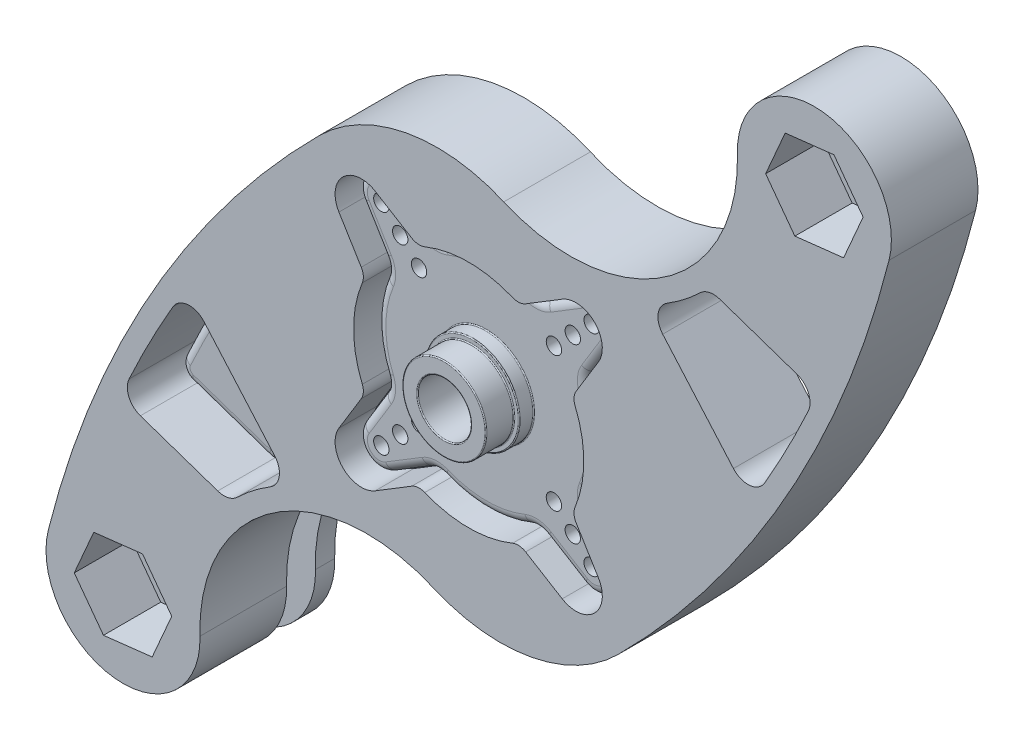
SolidWorks part; units mm, degrees
ref_plane "Front Plane" through (0, 0, 0) normal (0, 0, 1) x (1, 0, 0)
ref_plane "Top Plane" through (0, 0, 0) normal (0, 1, 0) x (1, 0, 0)
ref_plane "Right Plane" through (0, 0, 0) normal (1, 0, 0) x (0, 0, -1)
sketch "Sketch2" plane through (0, 0, 0) normal (0, 0, 1) x (1, 0, 0)
  line L1 (0, 0) -> (14.055, 0)
  line L2 (0, 0) -> (0, 14.055)
  line L3 (0, 14.055) -> (14.055, 14.055)
  line L4 (14.055, 0) -> (14.055, 14.055)
  dimension "D1" = 14.055
  dimension "D2" = 14.055
extrude "Boss-Extrude1" add sketch "Sketch2" along normal blind 2.15
sketch "Sketch3" plane through (0, 0, 2.15) normal (0, 0, 1) x (1, 0, 0)
  line L1 (14.055, 0) -> (14.055, 14.055) construction
  line L2 (0.9991, 9.98) -> (3.8759, 5.2647)
  line L3 (4.075, 13.0559) -> (8.7903, 10.1791)
  line L4 (0, 14.055) -> (14.055, 0) construction
  line L5 (14.055, 11.46) -> (14.055, 14.055)
  line L6 (14.055, 14.055) -> (0, 14.055)
  line L7 (0, 14.055) -> (0, 0)
  line L8 (0, 0) -> (2.595, 0)
  line L10 (0, 0) -> (14.055, 0) construction
  arc A0 (14.055, 11.46) -> (2.595, 0) centre (14.055, 0) ccw construction
  arc A1 (0.9991, 9.98) -> (4.075, 13.0559) centre (2.9095, 11.1455) cw
  arc A2 (3.8759, 5.2647) -> (2.595, 0) centre (14.055, 0) ccw
  arc A3 (8.7903, 10.1791) -> (14.055, 11.46) centre (14.055, 0) cw
  point P11 (1.3271, 12.7279)
  dimension "D1" = 11.46
  dimension "D4" = 18
  dimension "D2" = 6.95
  dimension "D3" = 4.35
extrude "Cut-Extrude3" cut sketch "Sketch3" against normal blind 2.15
sketch "Sketch4" plane through (0, 0, 2.15) normal (0, 0, 1) x (1, 0, 0)
  line L0 (14.055, 0) -> (14.055, 11.46) construction
  line L1 (2.595, 0) -> (14.055, 0) construction
  arc A0 (14.055, 1.56) -> (12.495, 0) centre (14.055, 0) ccw
  dimension "D1" = 1.56
extrude "Cut-Extrude1" cut sketch "Sketch4" against normal blind 2.15 and the other way through all
sketch "Sketch5" plane through (0, 0, 2.15) normal (0, 0, 1) x (1, 0, 0)
  line L0 (1.3271, 12.7279) -> (12.9519, 1.1031) construction
  circle A0 centre (7.0476, 7.0074) radius 0.8
  circle A1 centre (5.0889, 8.9661) radius 0.8
  circle A2 centre (3.1302, 10.9248) radius 0.8
  arc A3 (4.075, 13.0559) -> (0.9991, 9.98) centre (2.9095, 11.1455) ccw construction
  arc A4 (14.055, 1.56) -> (12.495, 0) centre (14.055, 0) ccw construction
  dimension "D1" = 1.6
  dimension "D3" = 2.77
  dimension "D2" = 2.55
  dimension "D4" = 2.77
extrude "Cut-Extrude4" cut sketch "Sketch5" against normal blind 2.15
fillet "Fillet1" radius 2 2 edges at (8.7903, 10.1791, 1.075) (3.8759, 5.2647, 1.075)
fillet "Fillet2" radius 1 7 edges at (2.8137, 2.2282, 2.15) (3.6066, 5.2905, 2.15) (2.1596, 8.0779, 2.15) (1.3271, 12.7279, 2.15) (5.9771, 11.8954, 2.15) (8.7645, 10.4484, 2.15) (11.8268, 11.2413, 2.15)
sketch "Sketch6" plane through (0, 0, 2.15) normal (0, 0, 1) x (1, 0, 0)
  line L2 (14.055, 1.56) -> (14.055, 10.46) construction
  line L3 (3.595, 0) -> (12.495, 0) construction
  line L4 (14.055, 4.9) -> (14.055, 2.765)
  line L5 (11.29, 0) -> (9.155, 0)
  arc A0 (14.055, 2.765) -> (11.29, 0) centre (14.055, 0) ccw
  arc A1 (14.055, 4.9) -> (9.155, 0) centre (14.055, 0) ccw
  dimension "D1" = 2.765
  dimension "D2" = 4.9
extrude "Boss-Extrude2" add sketch "Sketch6" along normal blind 1.5
sketch "Sketch7" plane through (0, 0, 3.65) normal (0, 0, 1) x (1, 0, 0)
  line L0 (14.055, 2.765) -> (14.055, 4.9) construction
  line L1 (9.155, 0) -> (11.29, 0) construction
  line L2 (14.055, 4.35) -> (14.055, 2.765)
  line L3 (11.29, 0) -> (9.705, 0)
  arc A0 (14.055, 2.765) -> (11.29, 0) centre (14.055, 0) ccw
  arc A1 (14.055, 2.765) -> (11.29, 0) centre (14.055, 0) ccw construction
  arc A2 (14.055, 4.35) -> (9.705, 0) centre (14.055, 0) ccw
  dimension "D1" = 4.35
extrude "Boss-Extrude3" add sketch "Sketch7" along normal blind 2.9
fillet "Fillet3" radius 0.1 5 edges at (10.5902, 3.4648, 2.15) (10.5902, 3.4648, 3.65) (10.9791, 3.0759, 3.65) (12.0998, 1.9552, 6.55) (10.9791, 3.0759, 6.55)
sketch "Sketch8" plane through (0, 0, 0) normal (0, 0, -1) x (-1, 0, 0)
  line L0 (-14.055, 1.56) -> (-14.055, 11.46) construction
  line L1 (-2.595, 0) -> (-12.495, 0) construction
  line L2 (-12.495, 0) -> (-11.305, 0)
  line L3 (-14.055, 2.75) -> (-14.055, 1.56)
  arc A0 (-14.055, 1.56) -> (-12.495, 0) centre (-14.055, 0) cw
  arc A1 (-12.495, 0) -> (-14.055, 1.56) centre (-14.055, 0) ccw construction
  arc A2 (-14.055, 2.75) -> (-11.305, 0) centre (-14.055, 0) cw
  dimension "D1" = 2.75
extrude "Cut-Extrude5" cut sketch "Sketch8" against normal blind 1.4
mirror "Mirror1" about plane through (0, 0, 2.15) normal (0, 1, 0) of bodies 109 104
mirror "Mirror2" about plane through (14.055, 0, 2.15) normal (-1, 0, 0) of bodies 105
sketch "Sketch9" plane through (0, 0, 0) normal (0, 0, -1) x (-1, 0, 0)
  line L0 (21.866, -35.921) -> (-14.055, 0) construction
  line L1 (-14.055, 0) -> (-29.6113, -15.5563) construction
  line L2 (-29.6113, -15.5563) -> (-35.3919, -9.7758) construction
  line L3 (-14.055, 0) -> (1.5013, 15.5563) construction
  line L4 (1.5013, 15.5563) -> (-6.7407, 23.7984) construction
  line L5 (-27.1365, -13.0815) -> (-29.6113, -15.5563)
  line L6 (-0.9735, 13.0815) -> (1.5013, 15.5563)
  line L16 (-19.9704, 11.1618) -> (-23.7746, 13.4827)
  line L17 (-27.5377, 9.7196) -> (-25.2168, 5.9154)
  line L18 (-25.2168, -5.9154) -> (-27.5377, -9.7196)
  line L19 (-23.7746, -13.4827) -> (-19.9704, -11.1618)
  line L20 (-8.1396, -11.1618) -> (-4.3354, -13.4827)
  line L21 (-0.5723, -9.7196) -> (-2.8932, -5.9154)
  line L22 (-2.8932, 5.9154) -> (-0.5723, 9.7196)
  line L23 (-4.3354, 13.4827) -> (-8.1396, 11.1618)
  line L27 (-23.7746, -13.4827) -> (-19.9704, -11.1618)
  line L28 (-8.1396, -11.1618) -> (-4.3354, -13.4827)
  line L29 (-0.5723, -9.7196) -> (-2.8932, -5.9154)
  line L30 (-2.8932, 5.9154) -> (-0.5723, 9.7196)
  arc A0 (-29.6113, -15.5563) -> (-10.4093, -19.202) centre (-17.3331, -3.2781) ccw
  arc A1 (-10.4093, -19.202) -> (13.87, -35.6702) centre (-3.4855, -35.1259) cw
  arc A2 (13.87, -35.6702) -> (29.6221, -33.9607) centre (21.866, -35.921) ccw
  arc A3 (1.5013, 15.5563) -> (29.6221, -33.9607) centre (-74.2763, -60.2213) cw
  circle A12 centre (21.866, -35.921) radius 2.159
  arc A32 (-9.493, 11.0557) -> (-18.617, 11.0557) centre (-14.055, 0) ccw
  arc A33 (-19.9704, 11.1618) -> (-18.617, 11.0557) centre (-19.1892, 12.4423) ccw
  arc A34 (-23.7746, 13.4827) -> (-27.5377, 9.7196) centre (-25.2005, 11.1455) ccw
  arc A35 (-25.1107, 4.562) -> (-25.2168, 5.9154) centre (-26.4973, 5.1342) ccw
  arc A36 (-25.1107, 4.562) -> (-25.1107, -4.562) centre (-14.055, 0) ccw
  arc A37 (-25.2168, -5.9154) -> (-25.1107, -4.562) centre (-26.4973, -5.1342) ccw
  arc A38 (-27.5377, -9.7196) -> (-23.7746, -13.4827) centre (-25.2005, -11.1455) ccw
  arc A39 (-18.617, -11.0557) -> (-19.9704, -11.1618) centre (-19.1892, -12.4423) ccw
  arc A40 (-18.617, -11.0557) -> (-9.493, -11.0557) centre (-14.055, 0) ccw
  arc A41 (-8.1396, -11.1618) -> (-9.493, -11.0557) centre (-8.9208, -12.4423) ccw
  arc A42 (-4.3354, -13.4827) -> (-0.5723, -9.7196) centre (-2.9095, -11.1455) ccw
  arc A43 (-2.9993, -4.562) -> (-2.8932, -5.9154) centre (-1.6127, -5.1342) ccw
  arc A44 (-2.9993, -4.562) -> (-2.9993, 4.562) centre (-14.055, 0) ccw
  arc A45 (-2.8932, 5.9154) -> (-2.9993, 4.562) centre (-1.6127, 5.1342) ccw
  arc A46 (-0.5723, 9.7196) -> (-4.3354, 13.4827) centre (-2.9095, 11.1455) ccw
  arc A47 (-9.493, 11.0557) -> (-8.1396, 11.1618) centre (-8.9208, 12.4423) ccw
  arc A54 (-27.1365, -13.0815) -> (-23.7746, -13.4827) centre (-25.2005, -11.1455) ccw
  arc A55 (-18.617, -11.0557) -> (-19.9704, -11.1618) centre (-19.1892, -12.4423) ccw
  arc A56 (-18.617, -11.0557) -> (-9.493, -11.0557) centre (-14.055, 0) ccw
  arc A57 (-8.1396, -11.1618) -> (-9.493, -11.0557) centre (-8.9208, -12.4423) ccw
  arc A58 (-4.3354, -13.4827) -> (-0.5723, -9.7196) centre (-2.9095, -11.1455) ccw
  arc A59 (-2.9993, -4.562) -> (-2.8932, -5.9154) centre (-1.6127, -5.1342) ccw
  arc A60 (-2.9993, -4.562) -> (-2.9993, 4.562) centre (-14.055, 0) ccw
  arc A61 (-2.8932, 5.9154) -> (-2.9993, 4.562) centre (-1.6127, 5.1342) ccw
  arc A62 (-0.5723, 9.7196) -> (-0.9735, 13.0815) centre (-2.9095, 11.1455) ccw
  point P1 (-3.1302, -10.9248)
  dimension "D2" = 50.8
  dimension "D3" = 4.318
  dimension "D4" = 22
  dimension "D5" = 8
  dimension "D1" = 0.5
extrude "Boss-Extrude4" add sketch "Sketch9" against normal blind 4 and the other way blind 0.001 separate body
sketch "Sketch10" plane through (0, 0, -0.001) normal (0, 0, -1) x (-1, 0, 0)
  line L0 (1.5013, 15.5563) -> (-2.5645, 11.4905)
  line L1 (-3.6959, 10.3591) -> (-4.5232, 9.5318)
  line L2 (-5.6546, 8.4004) -> (-6.4819, 7.5731)
  line L3 (-7.6133, 6.4417) -> (-12.1105, 1.9445)
  line L4 (-15.9995, -1.9445) -> (-20.4967, -6.4417)
  line L5 (-21.6281, -7.5731) -> (-22.4554, -8.4004)
  line L6 (1.5013, 15.5563) -> (-0.9735, 13.0815)
  line L7 (-0.5723, 9.7196) -> (-2.8932, 5.9154)
  line L8 (-2.8932, -5.9154) -> (-0.5723, -9.7196)
  line L9 (-4.3354, -13.4827) -> (-8.1396, -11.1618)
  line L10 (-19.9704, -11.1618) -> (-23.7746, -13.4827)
  line L11 (-27.1365, -13.0815) -> (-29.6113, -15.5563)
  line L12 (-23.5868, -9.5318) -> (-24.4141, -10.3591)
  line L13 (-25.5455, -11.4905) -> (-29.6113, -15.5563)
  circle A0 centre (-3.1302, 10.9248) radius 0.8 construction
  circle A1 centre (-5.0889, 8.9661) radius 0.8 construction
  circle A2 centre (-7.0476, 7.0074) radius 0.8 construction
  circle A3 centre (-3.1302, -10.9248) radius 0.8 construction
  circle A4 centre (-5.0889, -8.9661) radius 0.8 construction
  circle A5 centre (-7.0476, -7.0074) radius 0.8 construction
  circle A6 centre (-24.9798, -10.9248) radius 0.8 construction
  circle A7 centre (-23.0211, -8.9661) radius 0.8 construction
  circle A8 centre (-21.0624, -7.0074) radius 0.8 construction
  circle A9 centre (-14.055, 0) radius 2.75 construction
  arc A10 (-3.6959, 10.3591) -> (-2.5645, 11.4905) centre (-3.1302, 10.9248) ccw
  arc A11 (-5.6546, 8.4004) -> (-4.5232, 9.5318) centre (-5.0889, 8.9661) ccw
  arc A12 (-7.6133, 6.4417) -> (-6.4819, 7.5731) centre (-7.0476, 7.0074) ccw
  arc A13 (-29.6113, -15.5563) -> (-10.4093, -19.202) centre (-17.3331, -3.2781) ccw
  arc A14 (13.87, -35.6702) -> (-10.4093, -19.202) centre (-3.4855, -35.1259) ccw
  arc A15 (13.87, -35.6702) -> (29.6221, -33.9607) centre (21.866, -35.921) ccw
  arc A16 (29.6221, -33.9607) -> (1.5013, 15.5563) centre (-74.2763, -60.2213) ccw
  arc A17 (-0.5723, 9.7196) -> (-0.9735, 13.0815) centre (-2.9095, 11.1455) ccw
  arc A18 (-2.8932, 5.9154) -> (-2.9993, 4.562) centre (-1.6127, 5.1342) ccw
  arc A19 (-2.9993, -4.562) -> (-2.9993, 4.562) centre (-14.055, 0) ccw
  arc A20 (-2.9993, -4.562) -> (-2.8932, -5.9154) centre (-1.6127, -5.1342) ccw
  arc A21 (-4.3354, -13.4827) -> (-0.5723, -9.7196) centre (-2.9095, -11.1455) ccw
  arc A22 (-8.1396, -11.1618) -> (-9.493, -11.0557) centre (-8.9208, -12.4423) ccw
  arc A23 (-18.617, -11.0557) -> (-9.493, -11.0557) centre (-14.055, 0) ccw
  arc A24 (-18.617, -11.0557) -> (-19.9704, -11.1618) centre (-19.1892, -12.4423) ccw
  arc A25 (-27.1365, -13.0815) -> (-23.7746, -13.4827) centre (-25.2005, -11.1455) ccw
  arc A26 (-29.6113, -15.5563) -> (-10.4093, -19.202) centre (-17.3331, -3.2781) ccw
  arc A27 (13.87, -35.6702) -> (-10.4093, -19.202) centre (-3.4855, -35.1259) ccw
  arc A28 (13.87, -35.6702) -> (29.6221, -33.9607) centre (21.866, -35.921) ccw
  arc A29 (29.6221, -33.9607) -> (1.5013, 15.5563) centre (-74.2763, -60.2213) ccw
  circle A30 centre (-3.1302, -10.9248) radius 0.8
  circle A31 centre (-5.0889, -8.9661) radius 0.8
  circle A32 centre (-7.0476, -7.0074) radius 0.8
  arc A33 (-25.5455, -11.4905) -> (-24.4141, -10.3591) centre (-24.9798, -10.9248) ccw
  arc A34 (-23.5868, -9.5318) -> (-22.4554, -8.4004) centre (-23.0211, -8.9661) ccw
  arc A35 (-21.6281, -7.5731) -> (-20.4967, -6.4417) centre (-21.0624, -7.0074) ccw
  arc A36 (-15.9995, -1.9445) -> (-12.1105, 1.9445) centre (-14.055, 0) ccw
  circle A37 centre (21.866, -35.921) radius 2.159 construction
  circle A38 centre (21.866, -35.921) radius 2.159
  dimension "D1" = 0
extrude "Boss-Extrude5" add sketch "Sketch10" along normal blind 5
sketch "Sketch13" plane through (0, 0, 4) normal (0, 0, 1) x (1, 0, 0)
  line L1 (-19.8364, -31.2445) -> (-24.9012, -31.825)
  line L2 (-24.9012, -31.825) -> (-26.9309, -36.5016)
  line L3 (-26.9309, -36.5016) -> (-23.8957, -40.5976)
  line L4 (-23.8957, -40.5976) -> (-18.8308, -40.017)
  line L5 (-18.8308, -40.017) -> (-16.8012, -35.3405)
  line L6 (-16.8012, -35.3405) -> (-19.8364, -31.2445)
  circle A0 centre (-21.866, -35.921) radius 4.415 construction
  dimension "D1" = 8.83
extrude "Cut-Extrude10" cut sketch "Sketch13" against normal blind 5.9531
sketch "Sketch15" plane through (0, 0, -5.001) normal (0, 0, -1) x (-1, 0, 0)
  line L0 (3.4053, -26.7266) -> (26.5984, -18.8078)
  line L1 (26.5984, -18.8078) -> (17.1337, -53.0342) construction
  circle A0 centre (21.866, -35.921) radius 2.159 construction
  arc A2 (26.5984, -18.8078) -> (5.3472, -46.1365) centre (36.791, -48.6607) cw
  arc A3 (5.3472, -46.1365) -> (3.4053, -26.7266) centre (-49.0114, -41.7728) ccw
  arc A4 (13.87, -35.6702) -> (-10.4093, -19.202) centre (-3.4855, -35.1259) ccw construction
  circle A5 centre (-14.055, 0) radius 2.75 construction
  point P2 (21.866, -35.921)
  point P8 (23.3651, -26.5147)
  point P9 (10.1802, -24.4134)
  point P10 (10.207, -24.4477)
  point P17 (20.3669, -45.3273)
  point P18 (23.3651, -26.5147)
  point P19 (2.2432, -23.1485)
  point P20 (5.522, -41.7393)
  point P21 (23.5236, -45.3007)
  point P22 (26.5984, -18.8078)
  dimension "D2" = 34.4
extrude "Cut-Extrude11" [suppressed] cut sketch "Sketch15" against normal blind 3.3
sketch "Sketch16" plane through (0, 0, -5.001) normal (0, 0, -1) x (-1, 0, 0)
  line L0 (3.4053, -26.7266) -> (26.5984, -18.8078) construction
  line L1 (10.1802, -24.4134) -> (24.8168, -19.4161) construction
  line L2 (1.0012, -18.3516) -> (15.5222, -1.7343) construction
  line L3 (10.8244, -22.0801) -> (22.1371, -18.2177)
  line L4 (4.4386, -17.4575) -> (15.2661, -5.0669)
  arc A0 (29.6221, -33.9607) -> (1.5013, 15.5563) centre (-74.2763, -60.2213) ccw construction
  arc A1 (13.87, -35.6702) -> (-10.4093, -19.202) centre (-3.4855, -35.1259) ccw construction
  arc A2 (22.1371, -18.2177) -> (15.2661, -5.0669) centre (-74.2763, -60.2213) ccw
  arc A3 (10.8244, -22.0801) -> (4.4386, -17.4575) centre (-3.4855, -35.1259) ccw
  arc A4 (24.8168, -19.4161) -> (15.5222, -1.7343) centre (-74.2763, -60.2213) ccw construction
  arc A5 (10.1802, -24.4134) -> (1.0012, -18.3516) centre (-3.4855, -35.1259) ccw construction
  point P2 (0, 0)
  dimension "D2" = 11
  dimension "D3" = 2
  dimension "D1" = 30
extrude "Cut-Extrude12" cut sketch "Sketch16" against normal through all
fillet "Fillet6" radius 2 4 edges at (-15.2661, -5.0669, -0.5005) (-22.1371, -18.2177, -0.5005) (-10.8244, -22.0801, -0.5005) (-4.4386, -17.4575, -0.5005)
sketch "Sketch17" [suppressed] plane through (0, 0, -8.001) normal (0, 0, -1) x (-1, 0, 0)
  line L10 (0.3154, -18.183) -> (11.3282, 4.2486)
  line L20 (11.6813, -4.1088) -> (5.8712, -15.943) construction
  arc A1 (24.8168, -19.4161) -> (1.5013, 15.5563) centre (-74.2763, -60.2213) ccw construction
  arc A10 (10.1802, -24.4134) -> (-10.4093, -19.202) centre (-3.4855, -35.1259) ccw construction
  arc A11 (13.87, -35.6702) -> (10.1802, -24.4134) centre (-3.4855, -35.1259) ccw construction
  arc A12 (13.87, -35.6702) -> (29.6221, -33.9607) centre (21.866, -35.921) ccw construction
  arc A13 (29.6221, -33.9607) -> (24.8168, -19.4161) centre (-74.2763, -60.2213) ccw construction
  arc A16 (24.8168, -19.4161) -> (11.3282, 4.2486) centre (-74.2763, -60.2213) ccw
  circle A17 centre (21.866, -35.921) radius 2.159 construction
  circle A18 centre (21.866, -35.921) radius 2.159
  arc A25 (10.1802, -24.4134) -> (0.3154, -18.183) centre (-3.4855, -35.1259) ccw
  arc A26 (13.87, -35.6702) -> (10.1802, -24.4134) centre (-3.4855, -35.1259) ccw
  arc A27 (13.87, -35.6702) -> (29.6221, -33.9607) centre (21.866, -35.921) ccw
  arc A28 (29.6221, -33.9607) -> (24.8168, -19.4161) centre (-74.2763, -60.2213) ccw
  point P1 (0, 0)
  dimension "D1" = 4
extrude "Boss-Extrude8" [suppressed] add sketch "Sketch17" along normal blind 2 from offset 0.1
sketch "Sketch18" [suppressed] plane through (0, 0, -8.101) normal (0, 0, 1) x (1, 0, 0)
  line L4 (-19.5763, -17.507) -> (-11.5378, -20.2515)
  line L5 (-6.32, -16.1634) -> (-12.1301, -4.3291)
  line L6 (-19.5763, -17.507) -> (-11.5378, -20.2515)
  line L7 (-6.32, -16.1634) -> (-12.1301, -4.3291)
  arc A12 (-6.5289, -16.8224) -> (-11.0285, -20.1375) centre (3.4855, -35.1259) ccw
  arc A13 (-11.5378, -20.2515) -> (-11.0285, -20.1375) centre (-11.3763, -19.7783) ccw
  arc A14 (-19.8688, -16.8245) -> (-19.5763, -17.507) centre (-19.4148, -17.0338) ccw
  arc A15 (-12.9999, -4.2797) -> (-19.8688, -16.8245) centre (74.2763, -60.2213) ccw
  arc A16 (-12.1301, -4.3291) -> (-12.9999, -4.2797) centre (-12.5789, -4.5495) ccw
  arc A17 (-6.5289, -16.8224) -> (-6.32, -16.1634) centre (-6.7689, -16.3837) ccw
  arc A18 (-6.5289, -16.8224) -> (-11.0285, -20.1375) centre (3.4855, -35.1259) ccw
  arc A19 (-11.5378, -20.2515) -> (-11.0285, -20.1375) centre (-11.3763, -19.7783) ccw
  arc A20 (-19.8688, -16.8245) -> (-19.5763, -17.507) centre (-19.4148, -17.0338) ccw
  arc A21 (-12.9999, -4.2797) -> (-19.8688, -16.8245) centre (74.2763, -60.2213) ccw
  arc A22 (-12.1301, -4.3291) -> (-12.9999, -4.2797) centre (-12.5789, -4.5495) ccw
  arc A23 (-6.5289, -16.8224) -> (-6.32, -16.1634) centre (-6.7689, -16.3837) ccw
  dimension "D1" = 0.5
extrude "Boss-Extrude11" [suppressed] add sketch "Sketch18" along normal blind 2
fillet "Fillet5" [suppressed] radius 0.5
sketch "Sketch20" [suppressed] plane through (0, 0, -4.701) normal (0, 0, -1) x (-1, 0, 0)
  circle A1 centre (21.866, -35.921) radius 3
  circle A2 centre (21.866, -35.921) radius 2.159 construction
  circle A3 centre (21.866, -35.921) radius 2.159
  dimension "D1" = 6
extrude "Boss-Extrude13" [suppressed] add sketch "Sketch20" along normal up to surface (3.3 mm away)
pattern_circular "CirPattern1" count 2 over 360 about axis through (14.055, 0, 0) along (0, 0, 1) of bodies 119
sketch "Sketch19" plane through (0, 0, -5.001) normal (0, 0, -1) x (-1, 0, 0)
  line L0 (-2.5645, 11.4905) -> (1.5013, 15.5563) construction
  line L1 (-1.0632, 15.0523) -> (0, 15.0523)
  line L2 (-1.0632, 15.0523) -> (-1.0632, 11.9945)
  line L3 (-1.0632, 11.9945) -> (0, 11.9945)
  line L4 (0, 15.0523) -> (0, 11.9945)
  line L5 (-1.0632, 15.0523) -> (0, 11.9945) construction
  line L6 (-1.0632, 11.9945) -> (0, 15.0523) construction
  line L7 (-29.6113, -15.5563) -> (-25.5455, -11.4905) construction
  line L8 (-29.3639, -11.7379) -> (-25.7929, -11.7379)
  line L9 (-29.3639, -11.7379) -> (-29.3639, -15.3089)
  line L10 (-29.3639, -15.3089) -> (-25.7929, -15.3089)
  line L11 (-25.7929, -11.7379) -> (-25.7929, -15.3089)
  line L12 (-29.3639, -11.7379) -> (-25.7929, -15.3089) construction
  line L13 (-29.3639, -15.3089) -> (-25.7929, -11.7379) construction
  point P0 (-0.5316, 13.5234)
  point P7 (-27.5784, -13.5234)
extrude "Boss-Extrude12" add sketch "Sketch19" against normal blind 4
sketch "Sketch21" plane through (0, 0, -5.001) normal (0, 0, -1) x (-1, 0, 0)
  line L4 (4.5971, -14.2365) -> (1.0012, -18.3516)
  line L5 (11.9496, -5.8227) -> (4.5971, -14.2365)
  line L6 (11.9496, -5.8227) -> (4.5971, -14.2365)
  line L7 (11.9496, -5.8227) -> (15.5222, -1.7343)
  arc A3 (29.6221, -33.9607) -> (1.5013, 15.5563) centre (-74.2763, -60.2213) ccw construction
  circle A4 centre (21.866, -35.921) radius 2.159 construction
  arc A5 (13.87, -35.6702) -> (29.6221, -33.9607) centre (21.866, -35.921) ccw construction
  arc A6 (13.87, -35.6702) -> (-10.4093, -19.202) centre (-3.4855, -35.1259) ccw construction
  arc A7 (29.6221, -33.9607) -> (15.5222, -1.7343) centre (-74.2763, -60.2213) ccw
  circle A8 centre (21.866, -35.921) radius 2.159
  arc A9 (13.87, -35.6702) -> (29.6221, -33.9607) centre (21.866, -35.921) ccw
  arc A10 (13.87, -35.6702) -> (1.0012, -18.3516) centre (-3.4855, -35.1259) ccw
  dimension "D1" = 2
extrude "Boss-Extrude14" add sketch "Sketch21" along normal blind 2 from offset 3 separate body
sketch "Sketch22" plane through (0, 0, -8.001) normal (0, 0, 1) x (1, 0, 0)
  line L0 (-3.4053, -26.7266) -> (-26.5984, -18.8078) construction
  line L1 (-10.1802, -24.4134) -> (-24.8168, -19.4161)
  line L3 (-1.0012, -18.3516) -> (-15.5222, -1.7343)
  line L4 (-1.0012, -18.3516) -> (-15.5222, -1.7343)
  circle A0 centre (-21.866, -35.921) radius 2.159 construction
  circle A1 centre (-21.866, -35.921) radius 2.159
  circle A2 centre (-21.866, -35.921) radius 3
  arc A3 (-29.6221, -33.9607) -> (-13.87, -35.6702) centre (-21.866, -35.921) ccw
  arc A4 (-1.0012, -18.3516) -> (-13.87, -35.6702) centre (3.4855, -35.1259) ccw
  arc A5 (-15.5222, -1.7343) -> (-29.6221, -33.9607) centre (74.2763, -60.2213) ccw
  arc A7 (-1.0012, -18.3516) -> (-10.1802, -24.4134) centre (3.4855, -35.1259) ccw
  arc A8 (-15.5222, -1.7343) -> (-24.8168, -19.4161) centre (74.2763, -60.2213) ccw
  dimension "D2" = 6
  dimension "D1" = 0
extrude "Boss-Extrude15" add sketch "Sketch22" along normal offset from surface (2.99 mm away) 0.01 up to face at (14.055, 0, -5.001)
sketch "Sketch23" plane through (0, 0, -5.011) normal (0, 0, 1) x (1, 0, 0)
  line L8 (-11.8609, -21.1979) -> (-19.8994, -18.4533)
  line L9 (-13.8321, -7.4678) -> (-6.4797, -15.8816)
  line L10 (-11.8609, -21.1979) -> (-19.8994, -18.4533)
  line L11 (-13.8321, -7.4678) -> (-6.4797, -15.8816)
  arc A12 (-20.777, -16.4058) -> (-19.8994, -18.4533) centre (-19.4148, -17.0338) ccw
  arc A13 (-16.2591, -7.7021) -> (-20.777, -16.4058) centre (74.2763, -60.2213) ccw
  arc A14 (-13.8321, -7.4678) -> (-16.2591, -7.7021) centre (-14.9616, -8.4548) ccw
  arc A15 (-20.777, -16.4058) -> (-19.8994, -18.4533) centre (-19.4148, -17.0338) ccw
  arc A16 (-16.2591, -7.7021) -> (-20.777, -16.4058) centre (74.2763, -60.2213) ccw
  arc A17 (-13.8321, -7.4678) -> (-16.2591, -7.7021) centre (-14.9616, -8.4548) ccw
  arc A21 (-6.8302, -18.1505) -> (-6.4797, -15.8816) centre (-7.6092, -16.8686) ccw
  arc A22 (-6.8302, -18.1505) -> (-10.3328, -20.8559) centre (3.4855, -35.1259) ccw
  arc A23 (-11.8609, -21.1979) -> (-10.3328, -20.8559) centre (-11.3763, -19.7783) ccw
  arc A24 (-6.8302, -18.1505) -> (-6.4797, -15.8816) centre (-7.6092, -16.8686) ccw
  arc A25 (-6.8302, -18.1505) -> (-10.3328, -20.8559) centre (3.4855, -35.1259) ccw
  arc A26 (-11.8609, -21.1979) -> (-10.3328, -20.8559) centre (-11.3763, -19.7783) ccw
  dimension "D1" = 0.5
  dimension "D2" = 0.5
extrude "Boss-Extrude16" add sketch "Sketch23" along normal blind 4
fillet "Fillet7" radius 1 8 edges at (-15.1058, -6.9617, -1.011) (-10.1559, -11.6747, -1.011) (-6.1267, -17.0976, -1.011) (-8.6571, -19.4053, -1.011) (-11.0487, -21.2421, -1.011) (-15.8802, -19.8256, -1.011) (-20.7935, -17.6247, -1.011) (-18.62, -12.001, -1.011)
